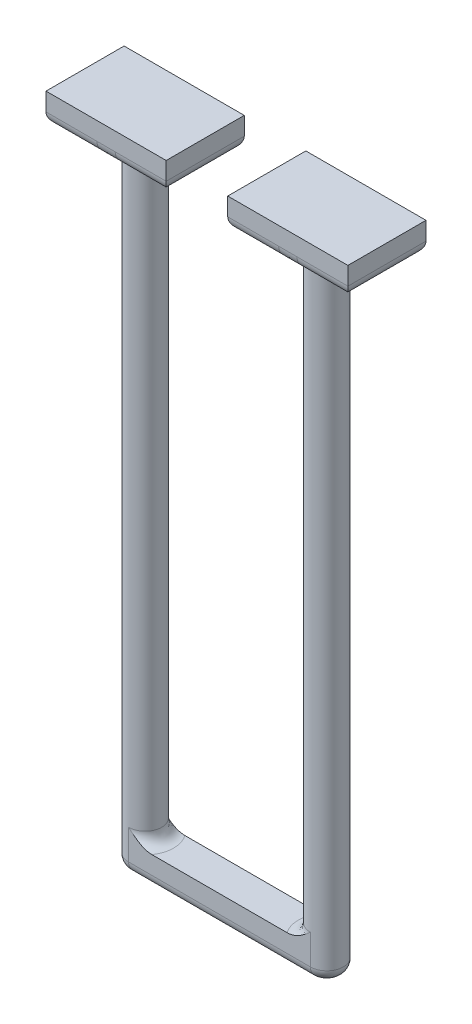
SolidWorks part; units mm, degrees
note: The reader was unsure of these and kept them because the rebuilt part matched: shared geometry of "Sketch1<5>", "Sketch1<6>".
ref_plane "Front Plane" through (0, 0, 0) normal (0, 0, 1) x (1, 0, 0)
ref_plane "Top Plane" through (0, 0, 0) normal (0, 1, 0) x (1, 0, 0)
ref_plane "Right Plane" through (0, 0, 0) normal (1, 0, 0) x (0, 0, -1)
sketch "Sketch1" plane through (0, 0, 0) normal (0, 1, 0) x (1, 0, 0)
  line L0 (0, 0) -> (15.125, 0) construction
  line L1 (0, 0) -> (0, 6.3857) construction
  line L2 (5.125, 6.5) -> (25.125, 6.5)
  line L3 (5.125, 6.5) -> (5.125, -6.5)
  line L4 (5.125, -6.5) -> (25.125, -6.5)
  line L5 (25.125, 6.5) -> (25.125, -6.5)
  line L6 (5.125, 6.5) -> (25.125, -6.5) construction
  line L7 (5.125, -6.5) -> (25.125, 6.5) construction
  line L8 (-25.125, 6.5) -> (-25.125, -6.5)
  line L9 (-5.125, -6.5) -> (-25.125, -6.5)
  line L10 (-5.125, 6.5) -> (-5.125, -6.5)
  line L11 (-5.125, 6.5) -> (-25.125, 6.5)
  line L12 (-5.125, -6.5) -> (-25.125, 6.5) construction
  line L13 (-5.125, 6.5) -> (-25.125, -6.5) construction
  line L14 (-15.125, -2.75) -> (15.125, -2.75)
  line L15 (15.125, -2.75) -> (15.125, 2.75)
  line L16 (15.125, 2.75) -> (-15.125, 2.75)
  line L17 (-15.125, 2.75) -> (-15.125, -2.75)
  circle A0 centre (15.125, 0) radius 2.75
  circle A1 centre (-15.125, 0) radius 2.75
  point P12 (-15.125, 0)
  dimension "D4" = 5.5
  dimension "D1" = 13
  dimension "D2" = 20
  dimension "D3" = 30.25
extrude "Boss-Extrude1" add sketch "Sketch1" along normal blind 5 contours L14 A1 L16 L10 L11 L8 L9 | A0 L14 L3 L4 L5 L2 L16 | L15 A0 | L15 A0 | A0 L16 L3 L14 | L16 A1 L14 L10 | A1 L17
extrude "Boss-Extrude2" add sketch "Sketch1<5>" against normal blind 105 contours A1 | A0 | A1 L17 | L15 A0
sketch "Sketch1<5>" plane through (0, 0, 0) normal (0, 1, 0) x (1, 0, 0) same geometry as "Sketch1"
extrude "Boss-Extrude3" add sketch "Sketch1<6>" along normal blind 5 from surface at -105 contours L3 L16 L10 L14 | L16 A1 L14 L10 | A0 L16 L3 L14 | L15 A0 | A1 L17 starting at face at (-15.125, -105, 2.75)
sketch "Sketch1<6>" plane through (0, 0, 0) normal (0, 1, 0) x (1, 0, 0) same geometry as "Sketch1"
fillet "Fillet1" radius 2 4 edges at (-17.875, -105, 0) (17.875, -105, 0) (0, -105, -2.75) (0, -105, 2.75)
fillet "Fillet2" radius 2 2 edges at (15.125, 0, 2.75) (-15.125, 0, 2.75)
fillet "Fillet3" radius 2 8 edges at (25.125, 0, 0) (5.125, 0, 0) (-5.125, 0, 0) (-25.125, 0, 0) (15.125, 0, 6.5) (15.125, 0, -6.5) (-15.125, 0, 6.5) (-15.125, 0, -6.5)
fillet "Fillet4" radius 2 2 edges at (-12.375, -100, 0) (12.375, -100, 0)
